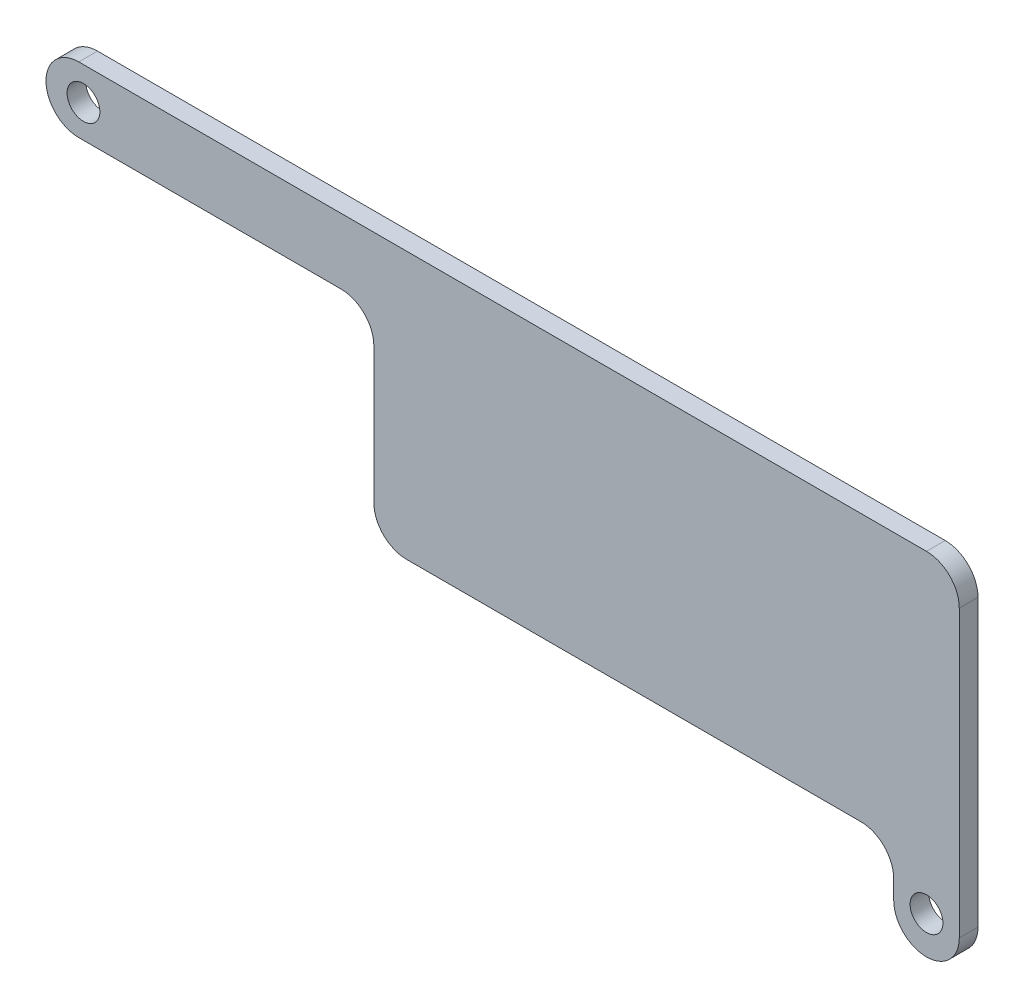
SolidWorks part; units mm, degrees
ref_plane "Plan de face" through (0, 0, 0) normal (0, 0, 1) x (1, 0, 0)
ref_plane "Plan de dessus" through (0, 0, 0) normal (0, 1, 0) x (1, 0, 0)
ref_plane "Plan de droite" through (0, 0, 0) normal (1, 0, 0) x (0, 0, -1)
sketch "Esquisse1" plane through (0, 0, 0) normal (0, 0, 1) x (1, 0, 0)
  line L0 (29.5, -12.5) -> (29.5, -17.5) construction
  line L1 (-29.5, 12.5) -> (29.5, 12.5) construction
  line L2 (-29.5, 12.5) -> (-29.5, -12.5)
  line L3 (-29.5, -12.5) -> (29.5, -12.5)
  line L4 (29.5, 12.5) -> (29.5, -12.5) construction
  line L5 (-29.5, 12.5) -> (-60.5, 12.5) construction
  line L6 (-29.5, 9) -> (-64.5, 9)
  line L7 (-64.5, 9) -> (-64.5, 16)
  line L8 (-64.5, 16) -> (-29.5, 16)
  line L9 (-29.5, 16) -> (-29.5, 12.5) construction
  line L10 (29.5, -12.5) -> (33, -12.5) construction
  line L11 (33, -12.5) -> (33, -21.5)
  line L12 (33, -21.5) -> (26, -21.5)
  line L13 (26, -21.5) -> (26, -12.5)
  line L14 (-29.5, 16) -> (33, 16)
  line L15 (33, 16) -> (33, -12.5)
  circle A0 centre (-60.5, 12.5) radius 1.75
  circle A1 centre (29.5, -17.5) radius 1.75
  point P4 (-29.5, 0)
  point P6 (0, 12.5)
  point P13 (-64.5, 12.5)
  point P20 (29.5, -21.5)
  point P21 (29.5, -39.6217)
  dimension "D4" = 3.5
  dimension "D1" = 59
  dimension "D2" = 25
  dimension "D3" = 31
  dimension "D5" = 7
  dimension "D6" = 35
  dimension "D7" = 9
  dimension "D8" = 5
extrude "Boss.-Extru.1" add sketch "Esquisse1" along normal blind 2 contours L15 L14 L8 L7 L6 L2 L3 L13 L12 L11 A1 A0 region at (-3.015, 2.4912, 0)
fillet "Congé1" radius 3.5 8 edges at (33, 16, 1) (26, -12.5, 1) (-29.5, -12.5, 1) (-29.5, 9, 1) (-64.5, 16, 1) (-64.5, 9, 1) (26, -21.5, 1) (33, -21.5, 1)
